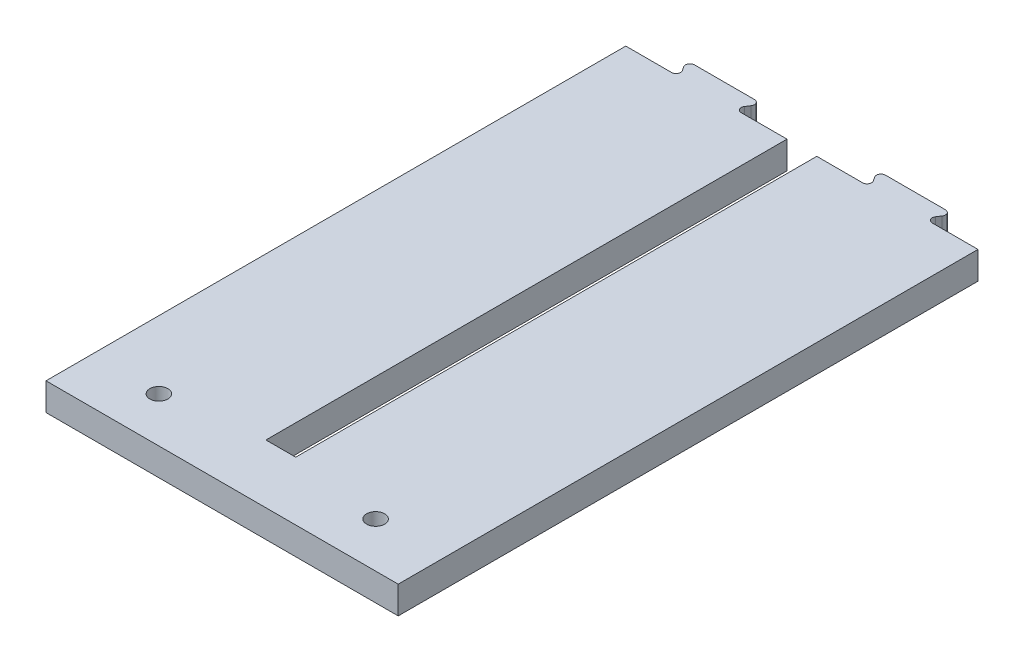
SolidWorks part; units mm, degrees
ref_plane "Front Plane" through (0, 0, 0) normal (0, 0, 1) x (1, 0, 0)
ref_plane "Top Plane" through (0, 0, 0) normal (0, 1, 0) x (1, 0, 0)
ref_plane "Right Plane" through (0, 0, 0) normal (1, 0, 0) x (0, 0, -1)
sketch "Sketch1" plane through (0, 0, 0) normal (0, 1, 0) x (1, 0, 0)
  line L1 (-19.5, 0) -> (19.5, 0)
  line L2 (-19.5, 0) -> (-19.5, 72.5)
  line L3 (-19.5, 72.5) -> (19.5, 72.5)
  line L4 (19.5, 0) -> (19.5, 72.5)
  point P5 (0, 0)
  dimension "D1" = 39
  dimension "D2" = 72.5
extrude "Boss-Extrude1" add sketch "Sketch1" along normal blind 3.05 contours L2 | L1 L4 L3 L2 | L4 region at (0, 0, -36.25)
sketch "Sketch4" plane through (0, 3.05, 0) normal (0, 1, 0) x (1, 0, 0)
  line L0 (-19.5, 72.5) -> (19.5, 72.5) construction
  line L2 (-19.5, 0) -> (19.5, 0) construction
  line L3 (1.65, 70.5) -> (-1.65, 70.5)
  line L4 (-1.65, 70.5) -> (-1.65, 69.5)
  line L5 (-1.65, 69.5) -> (1.65, 69.5)
  line L6 (1.65, 69.5) -> (1.65, 70.5)
  line L7 (0, 0) -> (0, 72.5) construction
  line L9 (1.65, 68.3) -> (-1.65, 68.3)
  line L10 (-1.65, 68.3) -> (-1.65, 6.5)
  line L11 (-1.65, 6.5) -> (1.65, 6.5)
  line L12 (1.65, 6.5) -> (1.65, 68.3)
  point P6 (0, 6.5)
  point P10 (0, 70.5)
  point P22 (0, 68.3)
  dimension "D1" = 2
  dimension "D2" = 1
  dimension "D3" = 1.2
  dimension "D4" = 3.3
  dimension "D7" = 6.5
extrude "Cut-Extrude1" cut sketch "Sketch4" against normal through all contours L5 L7 L3 L4 | L11 L7 L9 L10 | L7 L11 L12 L9 | L7 L5 L6 L3 | L6 L3 L4 L5 region at (0.825, 3.05, -70) region at (0.825, 3.05, -37.4) region at (-0.825, 3.05, -37.4) region at (-0.825, 3.05, -70)
sketch "Sketch7" plane through (0, 3.05, 0) normal (0, 1, 0) x (1, 0, 0)
  line L0 (0, 0) -> (-12, 0)
  line L1 (-19.5, 0) -> (19.5, 0) construction
  line L2 (-12, 0) -> (-12, 5)
  line L4 (0, 0) -> (0, 70) construction
  circle A0 centre (-12, 5) radius 1
  circle A2 centre (12, 5) radius 1
  dimension "D3" = 2
  dimension "D1" = 12
  dimension "D2" = 5
extrude "Cut-Extrude4" cut sketch "Sketch7" against normal through all contours A0 L2 | L2 A0 | A2 region at (-11.3129, 3.05, -4.3129)
sketch "Sketch8" plane through (0, 3.05, 0) normal (0, 1, 0) x (1, 0, 0)
  line L0 (19.5, 0) -> (19.5, 72.5) construction
  line L1 (-19.5, 72.5) -> (19.5, 72.5)
  line L2 (-19.5, 72.5) -> (-19.5, 64.2)
  line L3 (-19.5, 64.2) -> (19.5, 64.2)
  line L4 (19.5, 72.5) -> (19.5, 64.2)
  dimension "D1" = 8.3
extrude "Cut-Extrude5" cut sketch "Sketch8" against normal through all
sketch "Sketch9" plane through (0, 3.05, 0) normal (0, 1, 0) x (1, 0, 0)
  line L0 (-19.5, 64.2) -> (19.5, 64.2) construction
  line L1 (-19.5, 64.2) -> (-19.5, 66.2) construction
  line L2 (19.5, 64.2) -> (19.5, 66.2) construction
  line L3 (-19.5, 66.2) -> (19.5, 66.2) construction
  line L4 (-19.5, 64.2) -> (-13.5, 64.2)
  line L5 (-13.5, 64.2) -> (-14.825, 66.2)
  line L6 (-14.825, 66.2) -> (-6.325, 66.2)
  line L7 (-6.325, 66.2) -> (-7.65, 64.2)
  line L8 (-7.65, 64.2) -> (-1.65, 64.2)
  line L9 (1.65, 64.2) -> (7.65, 64.2)
  line L10 (7.65, 64.2) -> (6.325, 66.2)
  line L11 (6.325, 66.2) -> (14.825, 66.2)
  line L12 (14.825, 66.2) -> (13.5, 64.2)
  line L13 (13.5, 64.2) -> (19.5, 64.2)
  line L14 (-13.5, 64.2) -> (-7.65, 64.2)
  line L15 (7.65, 64.2) -> (13.5, 64.2)
  line L16 (-19.5, 66.2) -> (-14.825, 66.2)
  line L17 (14.825, 66.2) -> (19.5, 66.2)
  point P15 (-13, 64.2)
  point P19 (-8.15, 64.2)
  line M1 (-1.65, 64.2) -> (-19.5, 64.2)
  line M5 (19.5, 64.2) -> (1.65, 64.2)
  dimension "D1" = 2
  dimension "D2" = 4.675
  dimension "D3" = 8.5
  dimension "D4" = 6
extrude "Boss-Extrude3" add sketch "Sketch9" against normal blind 3.05 contours L7 L6 L5 M1 | L12 L11 L10 M5 region at (-10.575, 3.05, -65.2616) region at (10.575, 3.05, -65.2616)
fillet "Fillet2" radius 0.5 8 edges at (13.5, 1.525, -64.2) (-7.65, 1.525, -64.2) (14.825, 1.525, -66.2) (7.65, 1.525, -64.2) (6.325, 1.525, -66.2) (-6.325, 1.525, -66.2) (-14.825, 1.525, -66.2) (-13.5, 1.525, -64.2)
